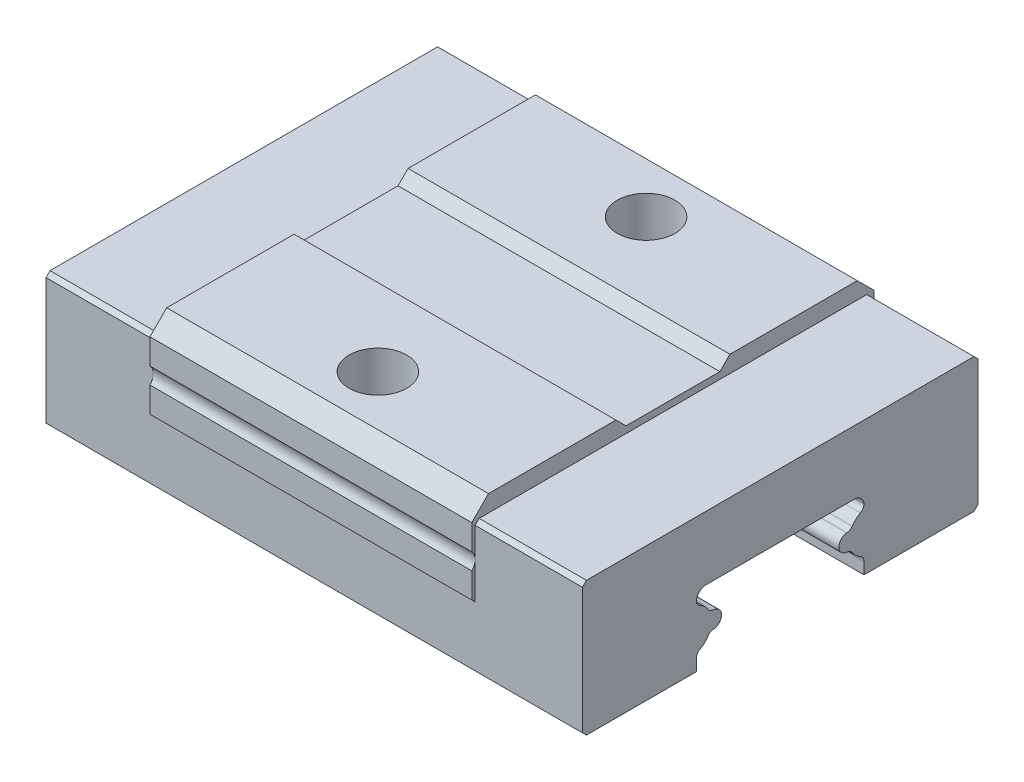
SolidWorks part; units mm, degrees
ref_plane "前视基准面" through (0, 0, 0) normal (0, 0, 1) x (1, 0, 0)
ref_plane "上视基准面" through (0, 0, 0) normal (0, 1, 0) x (1, 0, 0)
ref_plane "右视基准面" through (0, 0, 0) normal (1, 0, 0) x (0, 0, -1)
ref_plane "基准面4" through (0, 0, 0) normal (1, 0, 0) x (0, 0, -1)
sketch "草图1" plane through (0, 0, 0) normal (1, 0, 0) x (0, 0, -1)
  line L0 (0, 0) -> (0, 1.6077) construction
  line L1 (-5.9, 3.7) -> (5.9, 3.7)
  line L2 (-5.9, 3.7) -> (-5.9, -0.3)
  line L3 (-5.9, -0.3) -> (-2.5, -0.3)
  line L4 (5.9, 3.7) -> (5.9, -0.3)
  line L7 (2.5, -0.3) -> (5.9, -0.3)
  line L9 (-2.5, -0.3) -> (-2.5, 1.8)
  line L10 (2.5, 1.8) -> (-2.5, 1.8)
  line L15 (2.5, -0.3) -> (2.5, 1.8)
  dimension "D2" = 11.8
  dimension "D3" = 3.7
  dimension "D4" = 1.8
  dimension "D10" = 0.3
  dimension "D11" = 3.4
extrude "凸台-拉伸1" add sketch "草图1" along normal mid plane 16
sketch "草图2" plane through (0, 0, 0) normal (1, 0, 0) x (0, 0, -1)
  line L0 (5.9, -0.3) -> (5.9, 3.7) construction
  line L1 (-2.5, 1.8) -> (2.5, 1.8) construction
  line L2 (6, 1.7) -> (6, 3.7)
  line L3 (5.5, 4.2) -> (-5.5, 4.2)
  line L4 (-6, 1.7) -> (-6, 3.7)
  line L5 (0, 7.9178) -> (0, 0) construction
  line L6 (5.9, 1.6) -> (6, 1.7)
  line L7 (5.9, 3.7) -> (-5.9, 3.7) construction
  line L12 (-5.9, 1.6) -> (-6, 1.7)
  line L13 (-5.9, 3.7) -> (-5.9, -0.3) construction
  line L14 (-6, 3.7) -> (-5.5, 4.2)
  line L15 (6, 3.7) -> (5.5, 4.2)
  line L16 (-5.9, 1.6) -> (-5.9, 3.7)
  line L17 (-5.9, 3.7) -> (5.9, 3.7)
  line L18 (5.9, 3.7) -> (5.9, 1.6)
  dimension "D1" = 12
  dimension "D2" = 0.5
  dimension "D3" = 0.2
  dimension "D4" = 45
  dimension "D5" = 45
  dimension "D6" = 45
  dimension "D7" = 45
extrude "凸台-拉伸2" add sketch "草图2" along normal mid plane 9.6
sketch "草图11" plane through (8, 0, 0) normal (1, 0, 0) x (0, 0, -1)
  line L0 (-2, 1.042) -> (-2.1, 1.042)
  line L1 (-2, 0.542) -> (-2.1, 0.542)
  line L2 (-2.5, 1.4) -> (-2.5, 0.184)
  line L3 (-2.5, -0.3) -> (-2.5, 1.8) construction
  line L4 (0, 0) -> (0, 2.5786) construction
  line L5 (2.5, 1.4) -> (2.5, 0.184)
  line L6 (2, 0.542) -> (2.1, 0.542)
  line L7 (2, 1.042) -> (2.1, 1.042)
  line L8 (-2, 0.792) -> (-6.6736, 0.792) construction
  line L9 (-2.5, 1.8) -> (2.5, 1.8) construction
  arc A0 (-2, 0.542) -> (-2, 1.042) centre (-2, 0.792) ccw
  arc A1 (-2.5, 0.184) -> (-2.1, 0.542) centre (-2.684, 0.792) ccw
  arc A2 (-2.1, 1.042) -> (-2.5, 1.4) centre (-2.684, 0.792) ccw
  arc A3 (2.1, 1.042) -> (2.5, 1.4) centre (2.684, 0.792) cw
  arc A4 (2.5, 0.184) -> (2.1, 0.542) centre (2.684, 0.792) cw
  arc A5 (2, 0.542) -> (2, 1.042) centre (2, 0.792) cw
  dimension "D1" = 4
  dimension "D2" = 4.2
  dimension "D3" = 0.5
  dimension "D4" = 1.008
  dimension "D5" = 0.4
extrude "凸台-拉伸3" add sketch "草图11" against normal up to surface (16 mm away) up to face at (-8, 1.225, 0)
sketch "草图3" plane through (-4.8, 0, 0) normal (-1, 0, 0) x (0, 0, 1)
  line L0 (1.7, 4.2) -> (1.4, 3.9)
  line L1 (-5.5, 4.2) -> (5.5, 4.2) construction
  line L2 (-1.4, 3.9) -> (1.4, 3.9)
  line L3 (-1.7, 4.2) -> (1.7, 4.2)
  line L4 (0, 0) -> (0, 3.9193) construction
  line L5 (-1.7, 4.2) -> (-1.4, 3.9)
  line L6 (-5.5, 4.2) -> (5.5, 4.2) construction
  dimension "D1" = 3.4
  dimension "D2" = 45
  dimension "D3" = 0.3
extrude "切除-拉伸1" cut sketch "草图3" against normal through all
ref_plane "基准面6" through (0, 0, 0) normal (0, 0, 1) x (1, 0, 0)
sketch "草图5" plane through (0, 0, 0) normal (1, 0, 0) x (0, 0, -1)
  line L0 (-6, 2.7) -> (-8.9024, 2.7) construction
  line L1 (-6, 3.7) -> (-6, 1.7) construction
  line L2 (-5.9, 3.7) -> (-5.9, 1.6) construction
  circle A0 centre (-6.25, 2.7) radius 0.35
  dimension "D1" = 0.7
extrude "切除-拉伸2" cut sketch "草图5" along normal up to surface and the other way up to surface up to face at (4.8, 3.2857, 0) other way up to face at (-4.8, 3.2857, 0)
ref_plane "基准面5" through (4, 0, 0) normal (1, 0, 0) x (0, 0, -1)
sketch "草图7" plane through (4, 0, 0) normal (1, 0, 0) x (0, 0, -1)
  line L0 (-4.86, 4.2) -> (-4.86, 2.7)
  line L2 (-4.86, 2.7) -> (-4, 2.1833)
  line L3 (-4, 2.1833) -> (-4, 4.2)
  line L4 (-4, 4.2) -> (-4.86, 4.2)
  line L5 (-4, 2.1833) -> (-4, 5.7092) construction
  line L7 (-1.7, 4.2) -> (-5.5, 4.2) construction
  dimension "D1" = 59
  dimension "D2" = 1.72
  dimension "D3" = 4
  dimension "D4" = 1.5
revolve "切除-旋转1" [suppressed] cut sketch "草图7" angle 360 about L5
cosmetic thread "装饰螺纹线9" parameters "D2"=2
cosmetic thread "装饰螺纹线10" parameters "D2"=2
mirror "镜向1" [suppressed] about plane through (0, 0, 0) normal (1, 0, 0)
mirror "镜向2" [suppressed] about plane through (0, 0, 0) normal (0, 0, 1)
sketch "草图8" plane through (8, 0, 0) normal (1, 0, 0) x (0, 0, -1)
  line L0 (-3, 3.7) -> (-3, 1.201)
  line L1 (5.9, 3.7) -> (-5.9, 3.7) construction
  line L2 (3, 3.7) -> (3, 1.201)
  line L4 (0, 0) -> (0, 5.6166) construction
  line L5 (-3, 3.7) -> (3, 3.7)
  arc A0 (-3, 1.201) -> (3, 1.201) centre (0, 1.201) ccw
  dimension "D1" = 6
  dimension "D2" = 2.499
extrude "切除-拉伸3" [suppressed] cut sketch "草图8" against normal blind 1
chamfer "倒角1" distance 0.12 angle 45 6 edges at (6.4, 3.7, 5.9) (-6.4, 3.7, 5.9) (-6.4, 3.7, -5.9) (6.4, 3.7, -5.9) (0, -0.3, -5.9) (0, -0.3, 5.9)
mirror "镜向3" [suppressed] about plane through (0, 0, 0) normal (1, 0, 0)
sketch "草图10" plane through (0, 0, 0) normal (0, 0, 1) x (1, 0, 0)
  line L0 (-7, 1.2) -> (-12, 1.2)
  line L1 (-7, 1.2) -> (-7, -0.8)
  line L4 (-7, -0.8) -> (-10, -0.8)
  line L5 (-4.8, 3.7) -> (-8, 3.7) construction
  line L6 (-8, 3.58) -> (-8, -0.18) construction
  arc A1 (-12, 1.2) -> (-10, -0.8) centre (-10, 1.2) ccw
  dimension "D4" = 3
  dimension "D1" = 2.5
  dimension "D3" = 2
  dimension "D5" = 1
revolve "旋转1" [suppressed] add sketch "草图10" angle 360 about L0
fillet "圆角1" radius 0.2 8 edges at (0, 0.184, -2.5) (0, 0.542, -2.1) (0, 1.042, -2.1) (0, 1.4, -2.5) (0, 0.184, 2.5) (0, 0.542, 2.1) (0, 1.042, 2.1) (0, 1.4, 2.5)
fillet "圆角2" radius 0.3 2 edges at (0, 1.8, 2.5) (0, 1.8, -2.5)
pattern_linear "阵列(线性)1" [suppressed] count 1 spacing 21
sketch "草图12" plane through (0, 4.2, 0) normal (0, 1, 0) x (1, 0, 0)
  line L0 (0, 0) -> (-4.4901, 0) construction
  circle A0 centre (0, 4) radius 0.86
  circle A1 centre (0, -4) radius 0.86
  dimension "D1" = 1.72
  dimension "D2" = 8
extrude "切除-拉伸4" cut sketch "草图12" against normal blind 1.5
